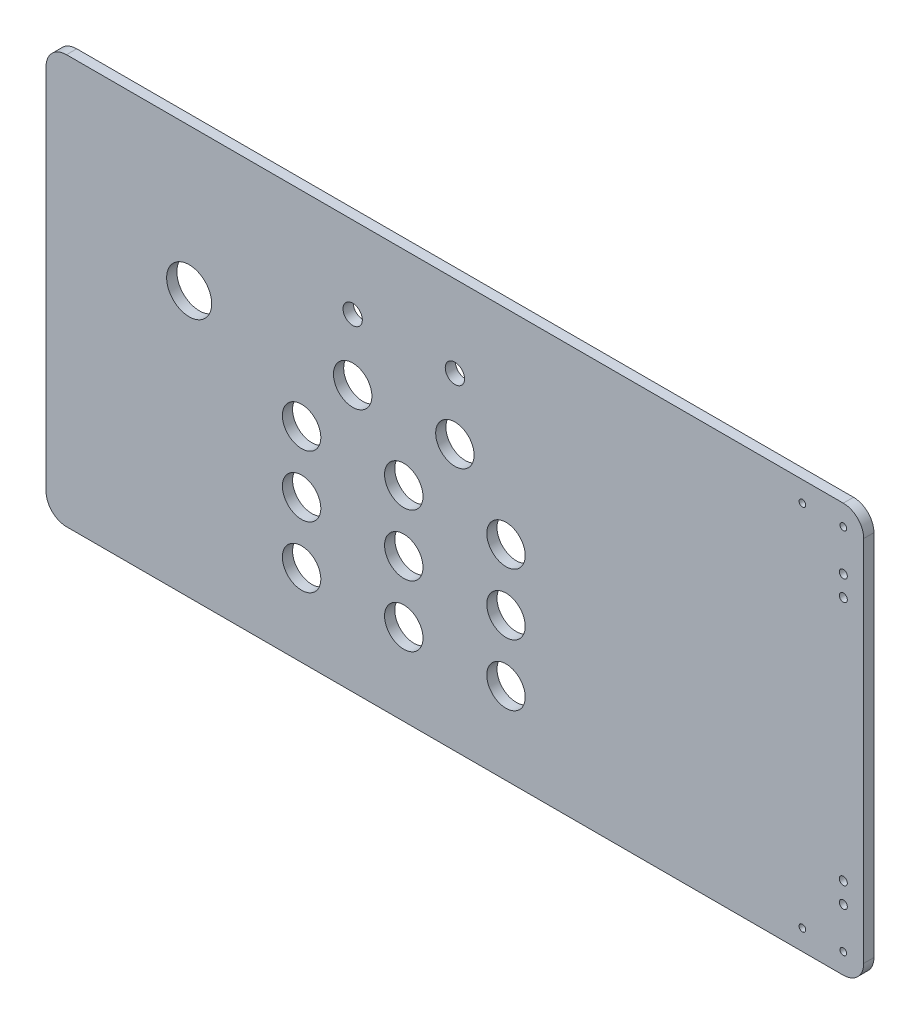
SolidWorks part; units mm, degrees
material "PC High Viscosity"
ref_plane "Front Plane" through (0, 0, 0) normal (0, 0, 1) x (1, 0, 0)
ref_plane "Top Plane" through (0, 0, 0) normal (0, 1, 0) x (1, 0, 0)
ref_plane "Right Plane" through (0, 0, 0) normal (1, 0, 0) x (0, 0, -1)
sketch "Sketch1" plane through (0, 0, 0) normal (0, 0, 1) x (1, 0, 0)
  line L1 (0, 0) -> (508, 0)
  line L2 (0, 0) -> (0, 254)
  line L3 (0, 254) -> (508, 254)
  line L4 (508, 0) -> (508, 254)
  dimension "D1" = 508
  dimension "D2" = 254
extrude "Boss-Extrude1" add sketch "Sketch1" along normal blind 6.35
sketch "Sketch3" plane through (0, 0, 0) normal (0, 0, -1) x (-1, 0, 0)
  line L0 (0, 0) -> (-508, 0) construction
  line L11 (-508, 254) -> (0, 254) construction
  line L17 (0, 254) -> (0, 0) construction
  line L18 (-508, 0) -> (-508, 254) construction
  line L19 (0, 254) -> (-25.4, 254) construction
  line L20 (0, 254) -> (0, 0) construction
  line L21 (0, 0) -> (-25.4, 0) construction
  line L22 (-25.4, 254) -> (-25.4, 0) construction
  line L23 (-508, 0) -> (-25.4, 0) construction
  line L24 (-508, 0) -> (-508, 25.4) construction
  line L25 (-508, 25.4) -> (-25.4, 25.4) construction
  line L26 (-25.4, 0) -> (-25.4, 25.4) construction
  line L27 (-508, 254) -> (-25.4, 254) construction
  line L28 (-508, 254) -> (-508, 228.6) construction
  line L29 (-508, 228.6) -> (-25.4, 228.6) construction
  line L30 (-25.4, 254) -> (-25.4, 228.6) construction
  circle A8 centre (-158.75, 88.9) radius 11.938
  circle A10 centre (-222.25, 88.9) radius 11.938
  circle A11 centre (-158.75, 50.8) radius 11.938
  circle A13 centre (-222.25, 50.8) radius 11.938
  circle A15 centre (-222.25, 127) radius 11.938
  circle A16 centre (-285.75, 127) radius 11.938
  circle A17 centre (-285.75, 88.9) radius 11.938
  circle A18 centre (-285.75, 50.8) radius 11.938
  circle A19 centre (-254, 203.2) radius 6
  circle A20 centre (-190.5, 203.2) radius 6
  circle A21 centre (-158.75, 127) radius 11.938
  circle A23 centre (-190.5, 165.1) radius 11.938
  circle A24 centre (-254, 165.1) radius 11.938
  circle A27 centre (-88.9, 165.1) radius 14
  circle A28 centre (-88.9, 165.1) radius 49.25 construction
  dimension "D2" = 12
  dimension "D3" = 63.5
  dimension "D4" = 38.1
  dimension "D5" = 38.1
  dimension "D6" = 63.5
  dimension "D7" = 25.4
  dimension "D8" = 38.1
  dimension "D9" = 38.1
  dimension "D10" = 25.4
  dimension "D11" = 23.876
  dimension "D12" = 63.5
  dimension "D13" = 28
  dimension "D14" = 98.5
  dimension "D15" = 31.75
  dimension "D21" = 12
  dimension "D22" = 23.876
  dimension "D16" = 50.8
  dimension "D17" = 25.4
  dimension "D18" = 88.9
  dimension "D19" = 88.9
  dimension "D20" = 254
extrude "Cut-Extrude2" cut sketch "Sketch3" against normal through all contours A18 | A17 | A16 | A24 | A10 | A8 | A23 | A11 | A13 | A15 | A21 | A27 | A20 | A19 region at (158.75, 88.9, 0) region at (222.25, 88.9, 0) region at (158.75, 50.8, 0) region at (222.25, 50.8, 0) region at (285.75, 127, 0) region at (285.75, 88.9, 0) region at (285.75, 50.8, 0) region at (190.5, 165.1, 0) region at (254, 165.1, 0)
fillet "Fillet1" radius 12.7 4 edges at (508, 0, 3.175) (0, 0, 3.175) (0, 254, 3.175) (508, 254, 3.175)
sketch "Sketch4" plane through (0, 0, 0) normal (0, 0, -1) x (-1, 0, 0)
  line L8 (-508, 12.7) -> (-508, 241.3) construction
  line L11 (-495.3, 254) -> (-12.7, 254) construction
  line L12 (-618.7392, 127) -> (68.6032, 127) construction
  circle A2 centre (-495.3205, 241.3) radius 2.0701
  circle A3 centre (-469.9205, 241.3) radius 2.0701
  circle A6 centre (-495.3205, 215.9) radius 2.4892
  circle A7 centre (-495.3205, 203.2) radius 2.4892
  circle A16 centre (-469.9205, 12.7) radius 2.0701
  circle A17 centre (-495.3205, 50.8) radius 2.4892
  circle A18 centre (-495.3205, 38.1) radius 2.4892
  circle A19 centre (-495.3205, 12.7) radius 2.0701
  dimension "D2" = 12.6795
  dimension "D8" = 127
  dimension "D5" = 4.9784
  dimension "D6" = 4.1402
  dimension "D7" = 12.7
  dimension "D3" = 38.1
  dimension "D4" = 50.8
  dimension "D13" = 25.4
extrude "Cut-Extrude3" cut sketch "Sketch4" against normal through all
